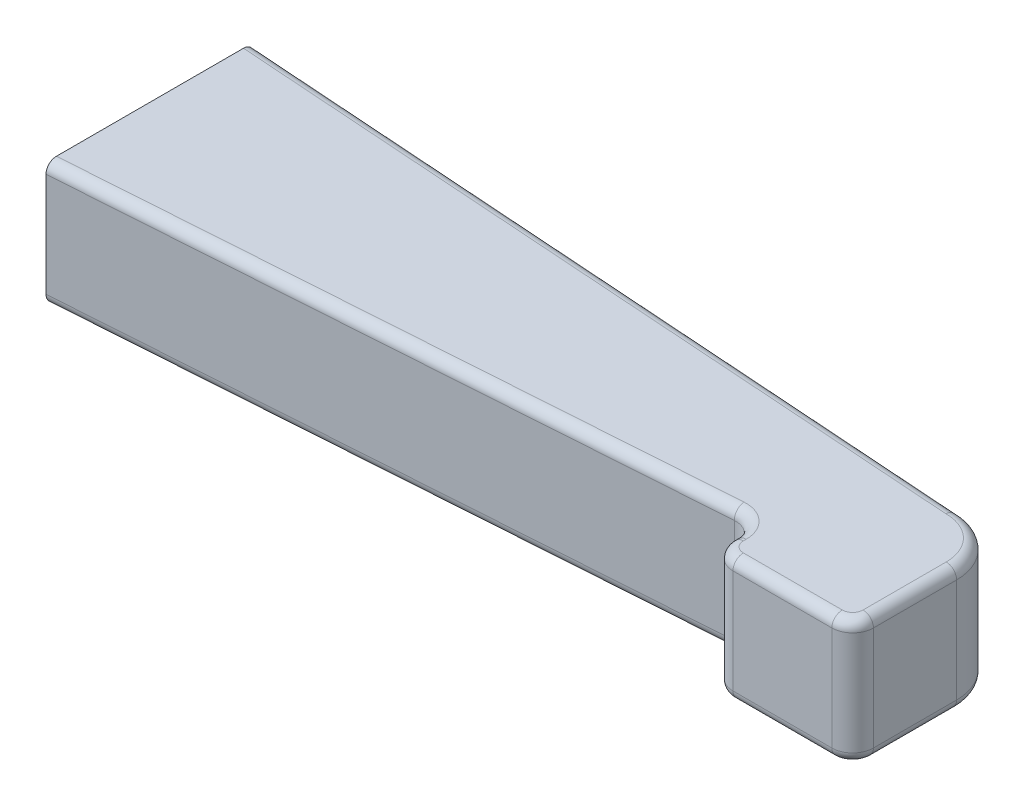
SolidWorks part; units mm, degrees
ref_plane "Front Plane" through (0, 0, 0) normal (0, 0, 1) x (1, 0, 0)
ref_plane "Top Plane" through (0, 0, 0) normal (0, 1, 0) x (1, 0, 0)
ref_plane "Right Plane" through (0, 0, 0) normal (1, 0, 0) x (0, 0, -1)
sketch "Sketch2" plane through (0, 0, 0) normal (0, 1, 0) x (1, 0, 0)
  line L0 (0, 0) -> (0, 10)
  line L2 (0, 10) -> (36.3004, 7.5)
  line L3 (0, 0) -> (36.3004, 2.5)
  arc A0 (36.3004, 7.5) -> (36.3004, 2.5) centre (36.3004, 5) cw
  point P5 (0, 5)
  dimension "D1" = 10
  dimension "D2" = 5
extrude "Boss-Extrude2" add sketch "Sketch2" along normal blind 6
ref_plane "Plane1" through (0, 3, 0) normal (0, -1, 0) x (-1, 0, 0)
sketch "Sketch3" plane through (0, 3, 0) normal (0, -1, 0) x (-1, 0, 0)
  line L0 (0, 8.25) -> (0, 1.75)
  line L1 (0, 10) -> (0, 0) construction
  line L3 (0, 8.25) -> (-12, 7.25)
  line L4 (0, 1.75) -> (-12, 2.75)
  arc A0 (-12, 7.25) -> (-12, 2.75) centre (-12, 5) ccw
  point P8 (0, 5)
  dimension "D1" = 6.5
  dimension "D2" = 1.75
  dimension "D3" = 4.5
extrude "Cut-Extrude1" cut sketch "Sketch3" against normal mid plane 2.25
ref_plane "Plane2" through (0, 0, -5) normal (0, 0, 1) x (1, 0, 0)
sketch "Sketch4" plane through (0, 0, -5) normal (0, 0, 1) x (1, 0, 0)
  line L0 (0, 0) -> (36.3004, 0) construction
  line L1 (38.8004, 6) -> (32.0436, 6)
  line L2 (38.8004, 6) -> (38.8004, 0)
  line L3 (38.8004, 0) -> (32.0436, 0)
  line L4 (32.0436, 6) -> (32.0436, 0)
extrude "Boss-Extrude3" add sketch "Sketch4" along normal blind 5
fillet "Fillet1" radius 1 3 edges at (32.0436, 3, -2.2068) (32.0436, 3, 0) (38.8004, 3, 0)
fillet "Fillet2" radius 0.5 18 edges at (38.5075, 0, -0.2929) (38.8004, 0, -3) (38.0682, 0, -6.7678) (18.1502, 0, -8.75) (15.4874, 0, -1.0666) (31.726, 0, -1.8666) (32.0436, 0, -1.0678) (32.3365, 0, -0.2929) (35.422, 0, 0) (31.726, 6, -1.8666) (15.4874, 6, -1.0666) (18.1502, 6, -8.75) (38.0682, 6, -6.7678) (38.8004, 6, -3) (38.5075, 6, -0.2929) (35.422, 6, 0) (32.3365, 6, -0.2929) (32.0436, 6, -1.0678)
